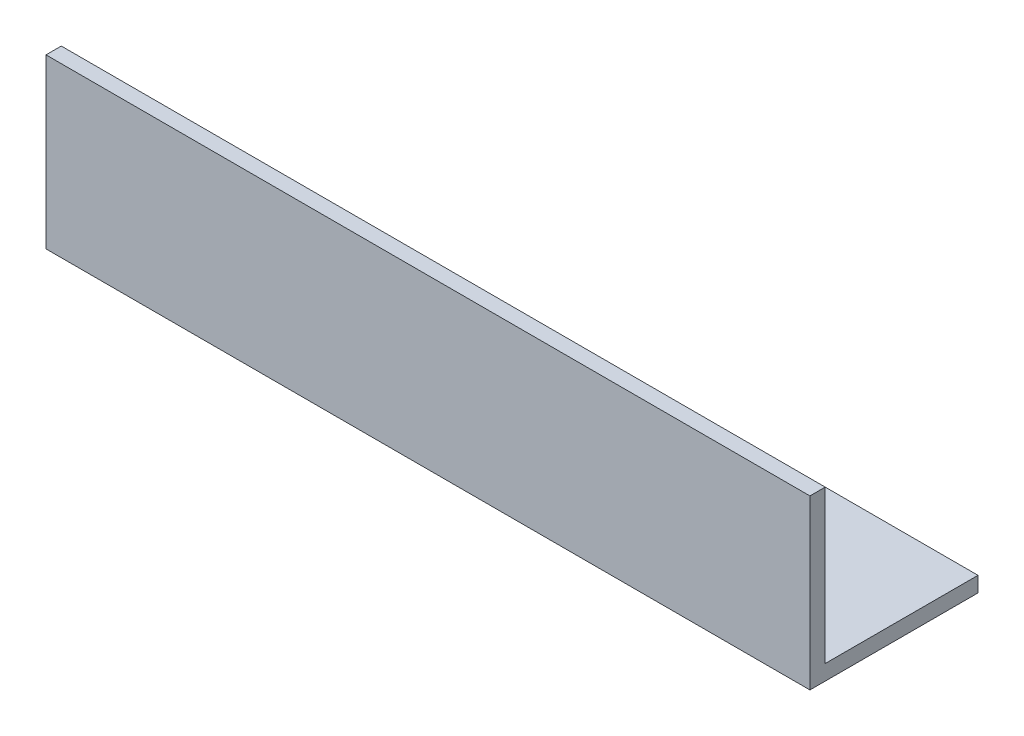
SolidWorks part; units mm, degrees
ref_plane "Спереди" through (0, 0, 0) normal (0, 0, 1) x (1, 0, 0)
ref_plane "Сверху" through (0, 0, 0) normal (0, 1, 0) x (1, 0, 0)
ref_plane "Справа" through (0, 0, 0) normal (1, 0, 0) x (0, 0, -1)
sketch "Эскиз1" plane through (0, 0, 0) normal (1, 0, 0) x (0, 0, -1)
  line L0 (0, 30) -> (0, 0)
  line L1 (0, 0) -> (30, 0)
extrude "Вытянуть-Тонкостенный1" add sketch "Эскиз1" along normal blind 150 thin thin type one direction wall 3
